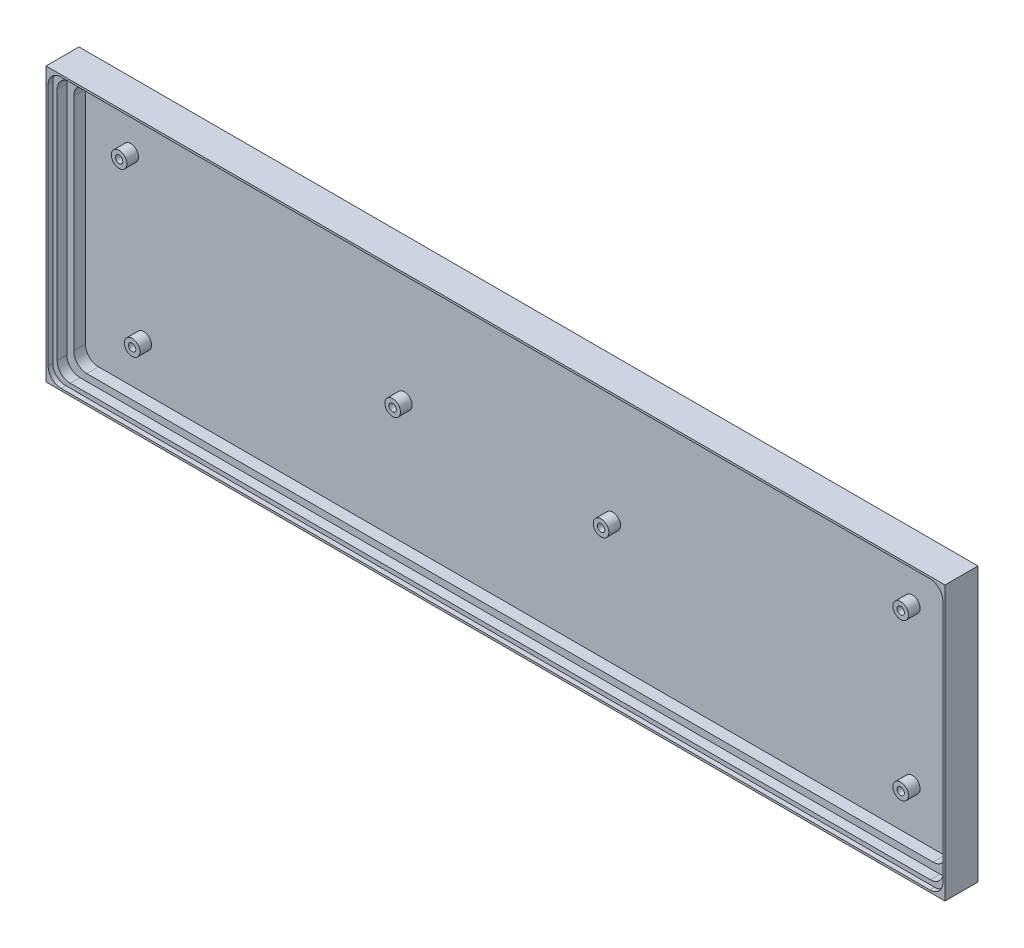
SolidWorks part; units mm, degrees
ref_plane "Front" through (0, 0, 0) normal (0, 0, 1) x (1, 0, 0)
ref_plane "Top" through (0, 0, 0) normal (0, 1, 0) x (1, 0, 0)
ref_plane "Right" through (0, 0, 0) normal (1, 0, 0) x (0, 0, -1)
sketch "Sketch1" plane through (0, 0, 0) normal (0, 0, 1) x (1, 0, 0)
  line L0 (164.338, 50.038) -> (-164.338, 50.038)
  line L1 (161.9885, -47.6885) -> (-161.9885, -47.6885)
  line L2 (161.9885, -47.6885) -> (161.9885, 47.6885)
  line L3 (161.9885, 47.6885) -> (-161.9885, 47.6885)
  line L4 (-161.9885, -47.6885) -> (-161.9885, 47.6885)
  line L5 (0, 47.6885) -> (0, -47.6885) construction
  line L6 (161.9885, 0) -> (-161.9885, 0) construction
  line L7 (163.576, -49.276) -> (-163.576, -49.276)
  line L8 (163.576, -49.276) -> (163.576, 49.276)
  line L9 (163.576, 49.276) -> (-163.576, 49.276)
  line L10 (-163.576, -49.276) -> (-163.576, 49.276)
  line L11 (0, 49.276) -> (0, -49.276) construction
  line L12 (163.576, 0) -> (-163.576, 0) construction
  line L13 (-164.338, -50.038) -> (-164.338, 50.038)
  line L14 (164.338, -50.038) -> (-164.338, -50.038)
  line L15 (164.338, -50.038) -> (164.338, 50.038)
  line L16 (159.4485, 45.1485) -> (-159.4485, 45.1485)
  line L17 (-159.4485, -45.1485) -> (-159.4485, 45.1485)
  line L18 (159.4485, -45.1485) -> (-159.4485, -45.1485)
  line L19 (159.4485, -45.1485) -> (159.4485, 45.1485)
  point P0 (0, 0)
  point P4 (0, 0)
  dimension "D1" = 95.377
  dimension "D2" = 323.977
  dimension "D3" = 1.5875
  dimension "D4" = 1.5875
  dimension "D5" = 0.762
  dimension "D6" = 2.54
extrude "Boss-Extrude1" add sketch "Sketch1" along normal blind 2.54 contours L4 L1 L2 L3 | L10 L7 L8 L9 L1 L4 L3 L2 | L14 L15 L0 L13 L7 L10 L9 L8 | L18 L19 L16 L17 region at (163.9944, 0, 0) region at (0, -47.3508, 0) region at (0, -48.9343, 0) region at (0, 0, 0)
extrude "Boss-Extrude2" add sketch "Sketch1<3>" along normal blind 12.065 contours L14 L15 L0 L13 L7 L10 L9 L8 region at (163.9944, 0, 0)
sketch "Sketch1<3>" plane through (0, 0, 0) normal (0, 0, 1) x (1, 0, 0) same geometry as "Sketch1"
extrude "Boss-Extrude3" add sketch "Sketch1<4>" along normal offset from surface (10.3505 mm away) 1.7145 contours L10 L7 L8 L9 L1 L4 L3 L2 region at (0, -48.9343, 0) up to face at (0, 0, 12.065)
sketch "Sketch1<4>" plane through (0, 0, 0) normal (0, 0, 1) x (1, 0, 0) same geometry as "Sketch1"
extrude "Boss-Extrude4" add sketch "Sketch1<5>" along normal offset from surface (6.8072 mm away) 3.5433 contours L4 L1 L2 L3 L19 L18 L17 L16 region at (0, -47.3508, 0) up to face at (0, 0, 10.3505)
sketch "Sketch1<5>" plane through (0, 0, 0) normal (0, 0, 1) x (1, 0, 0) same geometry as "Sketch1"
fillet "Fillet1" radius 4.7625 12 edges at (-163.576, -49.276, 11.2077) (-161.9885, -47.6885, 8.5788) (161.9885, -47.6885, 8.5788) (163.576, -49.276, 11.2077) (161.9885, 47.6885, 8.5788) (163.576, 49.276, 11.2077) (-161.9885, 47.6885, 8.5788) (-163.576, 49.276, 11.2077) (-159.4485, -45.1485, 4.6736) (159.4485, -45.1485, 4.6736) (159.4485, 45.1485, 4.6736) (-159.4485, 45.1485, 4.6736)
sketch "Sketch2" plane through (0, 0, 2.54) normal (0, 0, 1) x (1, 0, 0)
  circle A0 centre (-142.875, 28.575) radius 1.3526
  circle A1 centre (-138.1125, -28.575) radius 1.3526
  circle A2 centre (-42.8625, 0) radius 1.3526
  circle A3 centre (33.3375, 0) radius 1.3526
  circle A4 centre (142.875, -28.575) radius 2.8575
  circle A5 centre (33.3375, 0) radius 2.8575
  circle A6 centre (142.875, 28.575) radius 2.8575
  circle A7 centre (-42.8625, 0) radius 2.8575
  circle A12 centre (142.875, -28.575) radius 1.3526
  circle A13 centre (142.875, 28.575) radius 1.3526
  circle A14 centre (-138.1125, -28.575) radius 2.8575
  circle A15 centre (-142.875, 28.575) radius 2.8575
  dimension "D2" = 2.7051
  dimension "D1" = 5.715
extrude "Boss-Extrude5" add sketch "Sketch2" along normal up to surface (4.2672 mm away) contours A4 A12 | A6 A13 | A7 A2 | A5 A3 | A15 A0 | A14 A1 region at (140.0983, -28.575, 2.54) region at (30.5608, 0, 2.54) region at (140.0983, 28.575, 2.54) region at (-45.6392, 0, 2.54) region at (-140.8892, -28.575, 2.54) region at (-145.6517, 28.575, 2.54) up to face at (0, 0, 6.8072)
